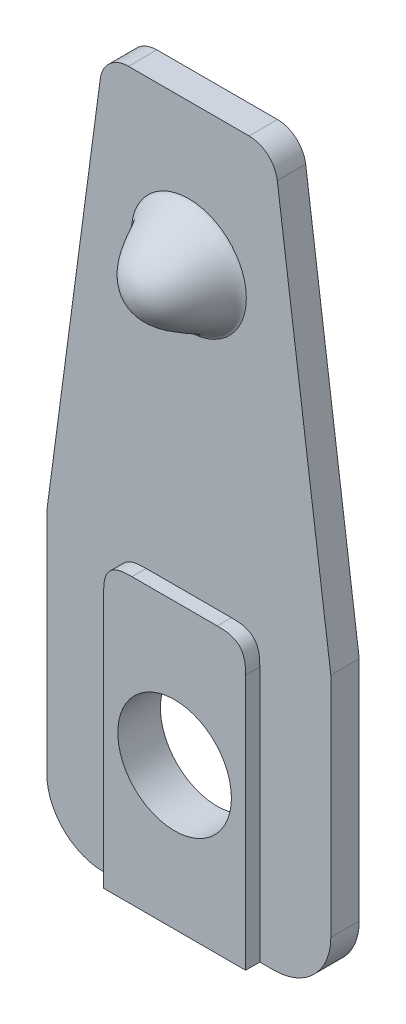
SolidWorks part; units mm, degrees
material "Maple"
ref_plane "Wasteboard" through (0, 0, 0) normal (0, 0, 1) x (1, 0, 0)
ref_plane "Left-Right" through (0, 0, 0) normal (0, 1, 0) x (1, 0, 0)
ref_plane "Front-Back" through (0, 0, 0) normal (1, 0, 0) x (0, 0, -1)
sketch "Sketch1" plane through (0, 0, 0) normal (0, 0, 1) x (1, 0, 0)
  line L0 (-3, -6.8603) -> (3, -6.8603)
  line L1 (5, -4.8603) -> (5, 3.1397)
  line L4 (2.1245, 18.1397) -> (-2.1245, 18.1397)
  line L5 (0, 0) -> (0, -2.6691) construction
  line L8 (-5, -4.8603) -> (-5, 3.1397)
  line L9 (-5, 3.1397) -> (-3.1157, 17.2719)
  line L10 (5, 3.1397) -> (3.1157, 17.2719)
  arc A0 (3, -6.8603) -> (5, -4.8603) centre (3, -4.8603) ccw
  arc A1 (-5, -4.8603) -> (-3, -6.8603) centre (-3, -4.8603) ccw
  arc A2 (3.1157, 17.2719) -> (2.1245, 18.1397) centre (2.1245, 17.1397) ccw
  arc A3 (-3.1157, 17.2719) -> (-2.1245, 18.1397) centre (-2.1245, 17.1397) cw
  point P11 (0, 18.1397)
  point P14 (0, -6.8603)
  dimension "D2" = 2
  dimension "D1" = 1
extrude "Boss-Extrude1" add sketch "Sketch1" along normal blind 1
sketch "Sketch3" plane through (0, 0, 1) normal (0, 0, 1) x (1, 0, 0)
  line L0 (-5, 3.1397) -> (5, 3.1397) construction
  line L1 (0, -6.8603) -> (0, 3.1397) construction
  line L2 (-3, -6.8603) -> (3, -6.8603) construction
  circle A0 centre (0, -1.8603) radius 2
  dimension "D1" = 4
sketch "Sketch4" plane through (0, 0, 1) normal (0, 0, 1) x (1, 0, 0)
  line L0 (-5, 3.1397) -> (5, 3.1397) construction
  line L1 (0, 3.1397) -> (0, -6.8603) construction
  line L2 (-3, -6.8603) -> (3, -6.8603) construction
  line L3 (2.5, -6.8603) -> (2.5, 3.1397)
  line L4 (2.5, 3.1397) -> (-2.5, 3.1397)
  line L5 (2.5, -6.8603) -> (-2.5, -6.8603)
  line L6 (-2.5, -6.8603) -> (-2.5, 3.1397)
  dimension "D1" = 2.5
extrude "Boss-Extrude2" add sketch "Sketch4" along normal blind 0.5
extrude "Cut-Extrude2" cut sketch "Sketch3" against normal through all both and the other way through all
sketch "Sketch5" plane through (0, 0, 1) normal (0, 0, 1) x (1, 0, 0)
  line L0 (0, 18.1397) -> (0, 13.1397) construction
  line L1 (2.1245, 18.1397) -> (-2.1245, 18.1397) construction
  circle A0 centre (0, 13.1397) radius 2 construction
  point P6 (0, 0)
  dimension "D1" = 5
sketch3d "3DSketch4"
  line L0 (0, 15.1648, 1) -> (0, 13.1397, 1)
  line L7 (0, 13.1397, 1) -> (0, 13.1397, 4.0653) construction
  line L8 (0, 13.1397, 1) -> (0, 13.1397, 3)
  spline S0 degree 3 poles (0, 13.1397, 3) (-0.0469, 14.2264, 2.8641) (-0.4641, 14.6092, 1.3599) (0, 15.1648, 1) knots 0 0 0 0 1 1 1 1
  point P0 (0, 13.1397, 1)
  dimension "D1" = 2
ref_plane "Plane2" through (0, 0, 0) normal (-1, 0, 0) x (0, 0, 1)
sketch "Sketch10" plane through (0, 0, 0) normal (-1, 0, 0) x (0, 0, 1)
  line L0 (3, 13.1397) -> (1, 13.1397)
  line L1 (1, 13.1397) -> (1, 15.1648)
  spline S0 degree 3 poles (1, 15.1648) (1.1035, 14.7767) (2.9513, 14.491) (3, 13.1397) knots 0 0 0 0 1 1 1 1
revolve "Revolve1" add sketch "Sketch10" angle 360 about L0
fillet "Fillet1" radius 1 2 edges at (2.5, 3.1397, 1.25) (-2.5, 3.1397, 1.25) curvature continuous yes
